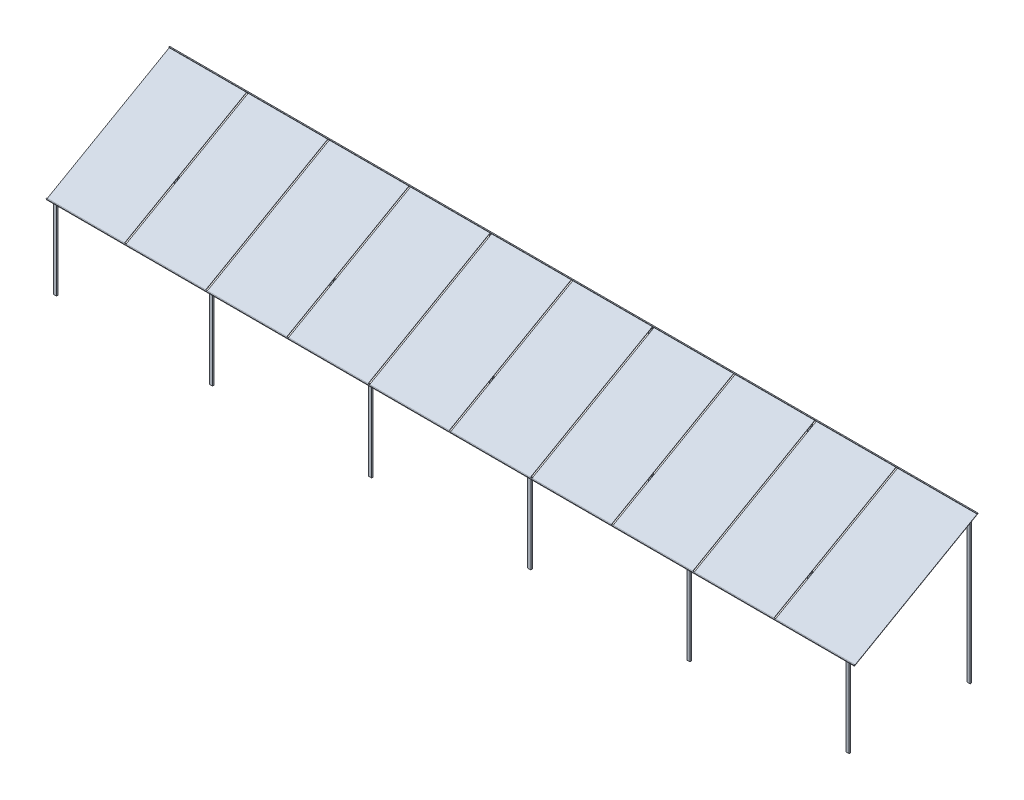
SolidWorks part; units mm, degrees
ref_plane "Front Plane" through (0, 0, 0) normal (0, 0, 1) x (1, 0, 0)
ref_plane "Top Plane" through (0, 0, 0) normal (0, 1, 0) x (1, 0, 0)
ref_plane "Right Plane" through (0, 0, 0) normal (1, 0, 0) x (0, 0, -1)
sketch "Sketch1" plane through (0, 0, 0) normal (0, 1, 0) x (1, 0, 0)
  line L0 (0, 0) -> (391.25, 0) construction
  line L1 (0, 0) -> (0, 195) construction
  line L2 (4965, 765) -> (4995, 765)
  line L3 (4960, 770) -> (5000, 770)
  line L4 (4960, 770) -> (4960, 750)
  line L5 (4960, 750) -> (5000, 750)
  line L6 (5000, 770) -> (5000, 750)
  line L7 (4995, 765) -> (4995, 755)
  line L8 (4965, 755) -> (4995, 755)
  line L9 (4965, 765) -> (4965, 755)
  line L10 (4965, -765) -> (4965, -755)
  line L11 (4965, -755) -> (4995, -755)
  line L12 (4995, -765) -> (4995, -755)
  line L13 (5000, -770) -> (5000, -750)
  line L14 (4960, -750) -> (5000, -750)
  line L15 (4960, -770) -> (4960, -750)
  line L16 (4960, -770) -> (5000, -770)
  line L17 (4965, -765) -> (4995, -765)
  line L18 (-4965, -765) -> (-4995, -765)
  line L19 (-4960, -770) -> (-5000, -770)
  line L20 (-4960, -770) -> (-4960, -750)
  line L21 (-4960, -750) -> (-5000, -750)
  line L22 (-5000, -770) -> (-5000, -750)
  line L23 (-4995, -765) -> (-4995, -755)
  line L24 (-4965, -755) -> (-4995, -755)
  line L25 (-4965, -765) -> (-4965, -755)
  line L26 (-4965, 765) -> (-4965, 755)
  line L27 (-4965, 755) -> (-4995, 755)
  line L28 (-4995, 765) -> (-4995, 755)
  line L29 (-5000, 770) -> (-5000, 750)
  line L30 (-4960, 750) -> (-5000, 750)
  line L31 (-4960, 770) -> (-4960, 750)
  line L32 (-4960, 770) -> (-5000, 770)
  line L33 (-4965, 765) -> (-4995, 765)
  line L34 (2960, 770) -> (2960, 750)
  line L35 (2960, 770) -> (3000, 770)
  line L36 (3000, 770) -> (3000, 750)
  line L37 (2960, 750) -> (3000, 750)
  line L38 (2965, 755) -> (2995, 755)
  line L39 (2995, 765) -> (2995, 755)
  line L40 (2965, 765) -> (2995, 765)
  line L41 (2965, 765) -> (2965, 755)
  line L42 (2960, -750) -> (3000, -750)
  line L43 (3000, -770) -> (3000, -750)
  line L44 (2960, -770) -> (3000, -770)
  line L45 (2965, -765) -> (2995, -765)
  line L46 (2995, -765) -> (2995, -755)
  line L47 (2965, -755) -> (2995, -755)
  line L48 (2965, -765) -> (2965, -755)
  line L49 (2960, -770) -> (2960, -750)
  line L50 (960, 770) -> (960, 750)
  line L51 (960, 770) -> (1000, 770)
  line L52 (1000, 770) -> (1000, 750)
  line L53 (960, 750) -> (1000, 750)
  line L54 (965, 755) -> (995, 755)
  line L55 (995, 765) -> (995, 755)
  line L56 (965, 765) -> (995, 765)
  line L57 (965, 765) -> (965, 755)
  line L58 (960, -750) -> (1000, -750)
  line L59 (1000, -770) -> (1000, -750)
  line L60 (960, -770) -> (1000, -770)
  line L61 (965, -765) -> (995, -765)
  line L62 (995, -765) -> (995, -755)
  line L63 (965, -755) -> (995, -755)
  line L64 (965, -765) -> (965, -755)
  line L65 (960, -770) -> (960, -750)
  line L66 (-1040, 770) -> (-1040, 750)
  line L67 (-1040, 770) -> (-1000, 770)
  line L68 (-1000, 770) -> (-1000, 750)
  line L69 (-1040, 750) -> (-1000, 750)
  line L70 (-1035, 755) -> (-1005, 755)
  line L71 (-1005, 765) -> (-1005, 755)
  line L72 (-1035, 765) -> (-1005, 765)
  line L73 (-1035, 765) -> (-1035, 755)
  line L74 (-1040, -750) -> (-1000, -750)
  line L75 (-1000, -770) -> (-1000, -750)
  line L76 (-1040, -770) -> (-1000, -770)
  line L77 (-1035, -765) -> (-1005, -765)
  line L78 (-1005, -765) -> (-1005, -755)
  line L79 (-1035, -755) -> (-1005, -755)
  line L80 (-1035, -765) -> (-1035, -755)
  line L81 (-1040, -770) -> (-1040, -750)
  line L82 (-3040, 770) -> (-3040, 750)
  line L83 (-3040, 770) -> (-3000, 770)
  line L84 (-3000, 770) -> (-3000, 750)
  line L85 (-3040, 750) -> (-3000, 750)
  line L86 (-3035, 755) -> (-3005, 755)
  line L87 (-3005, 765) -> (-3005, 755)
  line L88 (-3035, 765) -> (-3005, 765)
  line L89 (-3035, 765) -> (-3035, 755)
  line L90 (-3040, -750) -> (-3000, -750)
  line L91 (-3000, -770) -> (-3000, -750)
  line L92 (-3040, -770) -> (-3000, -770)
  line L93 (-3035, -765) -> (-3005, -765)
  line L94 (-3005, -765) -> (-3005, -755)
  line L95 (-3035, -755) -> (-3005, -755)
  line L96 (-3035, -765) -> (-3035, -755)
  line L97 (-3040, -770) -> (-3040, -750)
  dimension "D1" = 40
  dimension "D2" = 20
  dimension "D4" = 750
  dimension "D5" = 5000
  dimension "D3" = 5
  dimension "D6" = 5
extrude "Boss-Extrude1" add sketch "Sketch1" along normal blind 1000
sketch "Sketch2" plane through (0, 0, 0) normal (1, 0, 0) x (0, 0, -1)
  line L0 (-750, 1000) -> (750, 1000) construction
  line L1 (750, 1000) -> (750, 1866.0254) construction
  line L2 (750, 1866.0254) -> (-750, 1000) construction
  dimension "D1" = 30
extrude "Boss-Extrude2" add sketch "Sketch1<2>" along normal up to vertex (1866.0254 mm away) contours L31 L32 L29 L30 L33 L26 L27 L28 | L66 L69 L68 L67 L73 L72 L71 L70 | L50 L53 L52 L51 L57 L56 L55 L54 | L34 L37 L36 L35 L41 L40 L39 L38 | L4 L5 L6 L3 | L83 L84 L85 L82 region at (-4980, 0, -769.5528) region at (2980, 0, -769.5528) region at (980, 0, -769.5528) region at (-1020, 0, -769.5528) up to point (0, 1866.0254, -750)
sketch "Sketch1<2>" plane through (0, 0, 0) normal (0, 1, 0) x (1, 0, 0) same geometry as "Sketch1"
sketch "Sketch3" plane through (0, 0, 0) normal (0, 1, 0) x (1, 0, 0)
  line L0 (0, 0) -> (2644.5788, 0) construction
  line L1 (0, -847) -> (0, 847) construction
sketch "Sketch4" plane through (0, 0, 0) normal (1, 0, 0) x (0, 0, -1)
  line L0 (-778.6887, 995.0496) -> (773.7874, 1879.5783)
  line L1 (770, 1866.0254) -> (765.0987, 1874.6279) construction
  line L2 (-781.1639, 999.3939) -> (771.3122, 1883.9227)
  line L3 (-778.6887, 995.0496) -> (-781.1639, 999.3939)
  line L4 (773.7874, 1879.5783) -> (771.3122, 1883.9227)
  dimension "D1" = 10
  dimension "D2" = 10
  dimension "D3" = 5
extrude "Boss-Extrude3" add sketch "Sketch4" along normal mid plane 10151 separate body
sketch "Sketch5" plane through (0, 1090.4756, 621.3024) normal (0, 0.8689, 0.495) x (1, 0, 0)
  line L0 (4065.5, -183.988) -> (4065.5, 1602.7893) construction
  line L1 (5075.5, -183.988) -> (-5075.5, -183.988) construction
  line L2 (5075.5, 1602.7893) -> (-5075.5, 1602.7893) construction
  line L3 (4065.5, 1592.7893) -> (4065.5, -173.988)
  line L5 (4055.5, 1592.7893) -> (4055.5, -173.988)
  line L6 (4065.5, 1592.7893) -> (4055.5, 1592.7893)
  line L7 (4065.5, -173.988) -> (4055.5, -173.988)
  line L8 (4065.5, -173.988) -> (4075.5, -173.988)
  line L9 (4075.5, 1592.7893) -> (4075.5, -173.988)
  line L10 (4065.5, 1592.7893) -> (4065.5, -173.988)
  line L11 (4065.5, 1592.7893) -> (4075.5, 1592.7893)
  line L12 (3045.5, -173.988) -> (3035.5, -173.988)
  line L13 (3045.5, 1592.7893) -> (3045.5, -173.988)
  line L14 (3035.5, 1592.7893) -> (3035.5, -173.988)
  line L15 (3045.5, 1592.7893) -> (3045.5, -173.988)
  line L16 (3045.5, -173.988) -> (3055.5, -173.988)
  line L17 (3055.5, 1592.7893) -> (3055.5, -173.988)
  line L18 (3045.5, 1592.7893) -> (3035.5, 1592.7893)
  line L19 (3045.5, 1592.7893) -> (3055.5, 1592.7893)
  line L20 (2025.5, -173.988) -> (2015.5, -173.988)
  line L21 (2025.5, 1592.7893) -> (2025.5, -173.988)
  line L22 (2015.5, 1592.7893) -> (2015.5, -173.988)
  line L23 (2025.5, 1592.7893) -> (2025.5, -173.988)
  line L24 (2025.5, -173.988) -> (2035.5, -173.988)
  line L25 (2035.5, 1592.7893) -> (2035.5, -173.988)
  line L26 (2025.5, 1592.7893) -> (2015.5, 1592.7893)
  line L27 (2025.5, 1592.7893) -> (2035.5, 1592.7893)
  line L28 (1005.5, -173.988) -> (995.5, -173.988)
  line L29 (1005.5, 1592.7893) -> (1005.5, -173.988)
  line L30 (995.5, 1592.7893) -> (995.5, -173.988)
  line L31 (1005.5, 1592.7893) -> (1005.5, -173.988)
  line L32 (1005.5, -173.988) -> (1015.5, -173.988)
  line L33 (1015.5, 1592.7893) -> (1015.5, -173.988)
  line L34 (1005.5, 1592.7893) -> (995.5, 1592.7893)
  line L35 (1005.5, 1592.7893) -> (1015.5, 1592.7893)
  line L36 (-14.5, -173.988) -> (-24.5, -173.988)
  line L37 (-14.5, 1592.7893) -> (-14.5, -173.988)
  line L38 (-24.5, 1592.7893) -> (-24.5, -173.988)
  line L39 (-14.5, 1592.7893) -> (-14.5, -173.988)
  line L40 (-14.5, -173.988) -> (-4.5, -173.988)
  line L41 (-4.5, 1592.7893) -> (-4.5, -173.988)
  line L42 (-14.5, 1592.7893) -> (-24.5, 1592.7893)
  line L43 (-14.5, 1592.7893) -> (-4.5, 1592.7893)
  line L44 (-1034.5, -173.988) -> (-1044.5, -173.988)
  line L45 (-1034.5, 1592.7893) -> (-1034.5, -173.988)
  line L46 (-1044.5, 1592.7893) -> (-1044.5, -173.988)
  line L47 (-1034.5, 1592.7893) -> (-1034.5, -173.988)
  line L48 (-1034.5, -173.988) -> (-1024.5, -173.988)
  line L49 (-1024.5, 1592.7893) -> (-1024.5, -173.988)
  line L50 (-1034.5, 1592.7893) -> (-1044.5, 1592.7893)
  line L51 (-1034.5, 1592.7893) -> (-1024.5, 1592.7893)
  line L52 (-2054.5, -173.988) -> (-2064.5, -173.988)
  line L53 (-2054.5, 1592.7893) -> (-2054.5, -173.988)
  line L54 (-2064.5, 1592.7893) -> (-2064.5, -173.988)
  line L55 (-2054.5, 1592.7893) -> (-2054.5, -173.988)
  line L56 (-2054.5, -173.988) -> (-2044.5, -173.988)
  line L57 (-2044.5, 1592.7893) -> (-2044.5, -173.988)
  line L58 (-2054.5, 1592.7893) -> (-2064.5, 1592.7893)
  line L59 (-2054.5, 1592.7893) -> (-2044.5, 1592.7893)
  line L60 (-3074.5, -173.988) -> (-3084.5, -173.988)
  line L61 (-3074.5, 1592.7893) -> (-3074.5, -173.988)
  line L62 (-3084.5, 1592.7893) -> (-3084.5, -173.988)
  line L63 (-3074.5, 1592.7893) -> (-3074.5, -173.988)
  line L64 (-3074.5, -173.988) -> (-3064.5, -173.988)
  line L65 (-3064.5, 1592.7893) -> (-3064.5, -173.988)
  line L66 (-3074.5, 1592.7893) -> (-3084.5, 1592.7893)
  line L67 (-3074.5, 1592.7893) -> (-3064.5, 1592.7893)
  line L68 (-4094.5, -173.988) -> (-4104.5, -173.988)
  line L69 (-4094.5, 1592.7893) -> (-4094.5, -173.988)
  line L70 (-4104.5, 1592.7893) -> (-4104.5, -173.988)
  line L71 (-4094.5, 1592.7893) -> (-4094.5, -173.988)
  line L72 (-4094.5, -173.988) -> (-4084.5, -173.988)
  line L73 (-4084.5, 1592.7893) -> (-4084.5, -173.988)
  line L74 (-4094.5, 1592.7893) -> (-4104.5, 1592.7893)
  line L75 (-4094.5, 1592.7893) -> (-4084.5, 1592.7893)
  line L76 (-5114.5, -173.988) -> (-5124.5, -173.988)
  line L77 (-5114.5, 1592.7893) -> (-5114.5, -173.988)
  line L78 (-5124.5, 1592.7893) -> (-5124.5, -173.988)
  line L79 (-5114.5, 1592.7893) -> (-5114.5, -173.988)
  line L80 (-5114.5, -173.988) -> (-5104.5, -173.988)
  line L81 (-5104.5, 1592.7893) -> (-5104.5, -173.988)
  line L82 (-5114.5, 1592.7893) -> (-5124.5, 1592.7893)
  line L83 (-5114.5, 1592.7893) -> (-5104.5, 1592.7893)
  line L84 (5075.5, 1602.7893) -> (5075.5, -183.988) construction
  point P17 (4060.5, 1592.7893)
  dimension "D1" = 0
  dimension "D2" = 1000
  dimension "D5" = 10
  dimension "D6" = 10
  dimension "D3" = 10
  dimension "D4" = 10
ref_plane "Plane1" through (0, 351.1827, -616.3765) normal (0, 0.495, -0.8689) x (-1, 0, 0)
extrude "Cut-Extrude1" cut sketch "Sketch5" against normal blind 10 contours L67 L61 L64 L65 | L53 L58 L54 L52 | L59 L53 L56 L57 | L45 L50 L46 L44 | L51 L45 L48 L49 | L37 L42 L38 L36 | L43 L37 L40 L41 | L29 L34 L30 L28 | L35 L29 L32 L33 | L21 L26 L22 L20 | L27 L21 L24 L25 | L13 L18 L14 L12 | L19 L13 L16 L17 | L7 L3 L6 L5 | L11 L3 L8 L9 | L69 L68 L70 L74 | L73 L72 L71 L75 | L62 L60 L61 L66 region at (4070.5, 1441.6583, 4.9259) region at (4060.5, 1441.6583, 4.9259) region at (3040.5, 1441.6583, 4.9259) region at (3050.5, 1441.6583, 4.9259) region at (2020.5, 1441.6583, 4.9259) region at (2030.5, 1441.6583, 4.9259) region at (1000.5, 1441.6583, 4.9259) region at (1010.5, 1441.6583, 4.9259) region at (-19.5, 1441.6583, 4.9259) region at (-9.5, 1441.6583, 4.9259) region at (-1039.5, 1441.6583, 4.9259) region at (-1029.5, 1441.6583, 4.9259) region at (-2059.5, 1441.6583, 4.9259) region at (-2049.5, 1441.6583, 4.9259) region at (-3069.5, 1441.6583, 4.9259)
sketch "Sketch7" plane through (0, 1090.4756, 621.3024) normal (0, 0.8689, 0.495) x (1, 0, 0)
  line L0 (-5075.5, 1592.7893) -> (5075.5, 1592.7893)
  line L1 (-5075.5, 1602.7893) -> (-5075.5, -183.988) construction
  line L2 (5075.5, 1602.7893) -> (5075.5, -183.988) construction
  line L3 (5075.5, 1602.7893) -> (-5075.5, 1602.7893) construction
  line L4 (-5075.5, 1602.7893) -> (5075.5, 1602.7893)
  line L5 (-5075.5, 1592.7893) -> (-5075.5, 1602.7893)
  line L6 (5075.5, 1592.7893) -> (5075.5, 1602.7893)
  line L7 (-5075.5, 709.4006) -> (5075.5, 709.4006) construction
  line L8 (-5075.5, -173.988) -> (5075.5, -173.988)
  line L9 (-5075.5, -183.988) -> (5075.5, -183.988)
  line L10 (-5075.5, -173.988) -> (-5075.5, -183.988)
  line L11 (5075.5, -173.988) -> (5075.5, -183.988)
  dimension "D1" = 10
  dimension "D2" = 10
  dimension "D3" = 10
extrude "Boss-Extrude4" add sketch "Sketch7" along normal blind 10
